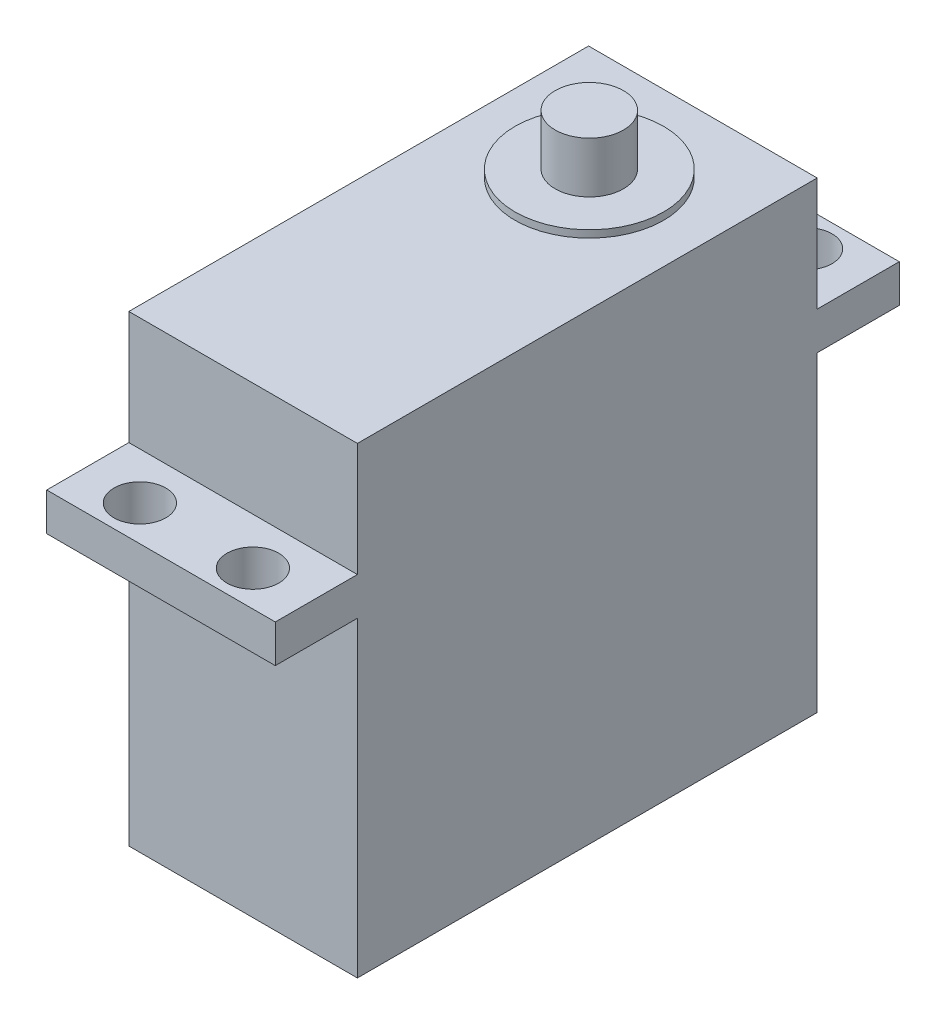
SolidWorks part; units mm, degrees
ref_plane "Front Plane" through (0, 0, 0) normal (0, 0, 1) x (1, 0, 0)
ref_plane "Top Plane" through (0, 0, 0) normal (0, 1, 0) x (1, 0, 0)
ref_plane "Right Plane" through (0, 0, 0) normal (1, 0, 0) x (0, 0, -1)
sketch "Sketch1" plane through (0, 0, 0) normal (1, 0, 0) x (0, 0, -1)
  line L0 (20.0533, 40.386) -> (20.0533, 0) construction
  line L1 (0, 0) -> (40.1066, 0)
  line L2 (0, 0) -> (0, 27.178)
  line L3 (0, 40.386) -> (40.1066, 40.386)
  line L4 (40.1066, 0) -> (40.1066, 27.178)
  line L5 (40.1066, 27.178) -> (47.2694, 27.178)
  line L6 (0, 30.48) -> (-7.1628, 30.48)
  line L8 (0, 27.178) -> (-7.1628, 27.178)
  line L9 (-7.1628, 30.48) -> (-7.1628, 27.178)
  line L10 (40.1066, 30.48) -> (47.2694, 30.48)
  line L11 (47.2694, 30.48) -> (47.2694, 27.178)
  line L12 (0, 30.48) -> (0, 40.386)
  line L13 (40.1066, 30.48) -> (40.1066, 40.386)
  dimension "D1" = 40.386
  dimension "D2" = 40.1066
  dimension "D3" = 54.4322
  dimension "D4" = 3.302
  dimension "D5" = 30.48
extrude "Boss-Extrude1" add sketch "Sketch1" along normal blind 19.939
sketch "Sketch2" plane through (0, 40.386, 0) normal (0, 1, 0) x (1, 0, 0)
  line L0 (19.939, 40.1066) -> (0, 40.1066) construction
  circle A0 centre (9.9695, 30.2006) radius 2.9782
  point P4 (9.9695, 40.1066)
  dimension "D1" = 5.9563
  dimension "D2" = 9.906
extrude "Boss-Extrude2" add sketch "Sketch2" along normal blind 5.08
sketch "Sketch3" plane through (0, 40.386, 0) normal (0, 1, 0) x (1, 0, 0)
  circle A0 centre (9.9695, 30.2006) radius 6.477
  circle A1 centre (9.9695, 30.2006) radius 2.9782 construction
  dimension "D1" = 12.954
extrude "Boss-Extrude3" add sketch "Sketch3" along normal blind 0.635
sketch "Sketch4" plane through (0, 30.48, 0) normal (0, 1, 0) x (1, 0, 0)
  line L0 (9.9695, 47.2694) -> (9.9695, -7.1628) construction
  line L1 (19.939, 47.2694) -> (0, 47.2694) construction
  line L2 (19.939, -7.1628) -> (0, -7.1628) construction
  line L3 (0, 44.1833) -> (19.939, 44.1833) construction
  line L4 (0, 47.2694) -> (0, 40.1066) construction
  line L5 (19.939, 47.2694) -> (19.939, 40.1066) construction
  line L6 (0, 20.0533) -> (19.939, 20.0533) construction
  line L7 (0, 40.1066) -> (0, 0) construction
  line L8 (19.939, 40.1066) -> (19.939, 0) construction
  circle A0 centre (5.0419, 44.1833) radius 2.2606
  circle A1 centre (14.8971, 44.1833) radius 2.2606
  circle A2 centre (14.8971, -4.0767) radius 2.2606
  circle A3 centre (5.0419, -4.0767) radius 2.2606
  dimension "D1" = 4.5212
  dimension "D2" = 9.8552
  dimension "D3" = 48.26
extrude "Cut-Extrude1" cut sketch "Sketch4" against normal through all
ref_plane "centerplane" through (9.9695, 0, 0) normal (-1, 0, 0) x (0, 0, 1)
ref_axis "center axis" through (9.9695, 45.466, -30.2006) along (0, -1, 0)
